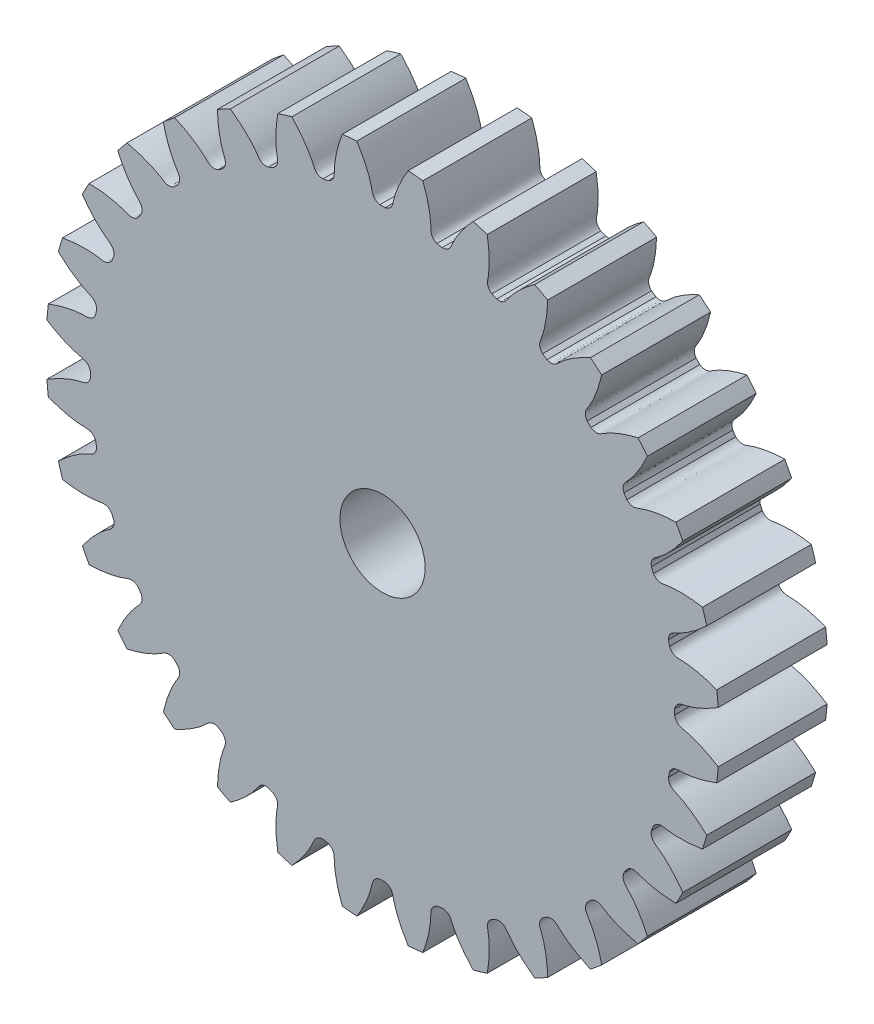
SolidWorks part; units mm, degrees
ref_plane "前视基准面" through (0, 0, 0) normal (0, 0, 1) x (1, 0, 0)
ref_plane "上视基准面" through (0, 0, 0) normal (0, 1, 0) x (1, 0, 0)
ref_plane "右视基准面" through (0, 0, 0) normal (1, 0, 0) x (0, 0, -1)
other "Configuration Table"
sketch "草图1" plane through (0, 0, 0) normal (0, 0, 1) x (1, 0, 0)
  circle A0 centre (0, 0) radius 8.5
extrude "凸台-拉伸1" add sketch "草图1" along normal blind 2.75
ref_axis "基准轴1" through (0, 0, 2.75) along (0, 0, -1)
sketch "草图2" plane through (0, 0, 0) normal (0, 0, 1) x (1, 0, 0)
  line L0 (0, 0) -> (0, 8.5) construction
  circle A0 centre (0, 0) radius 8.5 construction
  arc A1 (0.067, 7.3747) -> (-0.067, 7.3747) centre (0, 0) ccw
  arc A2 (1.6765, 9.6348) -> (-1.6765, 9.6348) centre (0, 0) ccw
  spline S0 degree 3 poles (0.067, 7.3747) (0.2444, 7.4176) (0.2542, 7.5462) (0.2867, 7.6804) (0.2952, 7.7127) (0.3051, 7.7477) (0.3166, 7.7854) (0.3299, 7.8257) (0.3449, 7.8686) (0.3618, 7.9139) (0.3807, 7.9618) (0.4017, 8.012) (0.4249, 8.0645) (0.4505, 8.1193) (0.4785, 8.1763) (0.509, 8.2353) (0.5421, 8.2964) (0.5779, 8.3594) (0.6164, 8.4243) (0.6579, 8.491) (0.7023, 8.5593) (0.7498, 8.6292) (0.8004, 8.7006) (0.8542, 8.7734) (0.9113, 8.8475) (0.9717, 8.9228) (1.0356, 8.9992) (1.1029, 9.0765) (1.1738, 9.1547) (1.2483, 9.2337) (1.3265, 9.3133) (1.4084, 9.3934) (1.5241, 9.5022) (1.6145, 9.5821) (1.6765, 9.6348) knots 0 0 0 0 0.124533 0.135329 0.147193 0.160126 0.174128 0.189198 0.205337 0.222544 0.24082 0.260164 0.280577 0.302059 0.324609 0.348227 0.372914 0.39867 0.425494 0.453386 0.482348 0.512377 0.543476 0.575642 0.608878 0.643181 0.678554 0.714995 0.752504 0.791082 0.830729 0.871444 0.913227 1 1 1 1
  spline S1 degree 3 poles (-0.067, 7.3747) (-0.2444, 7.4176) (-0.2542, 7.5462) (-0.2867, 7.6804) (-0.2952, 7.7127) (-0.3051, 7.7477) (-0.3166, 7.7854) (-0.3299, 7.8257) (-0.3449, 7.8686) (-0.3618, 7.9139) (-0.3807, 7.9618) (-0.4017, 8.012) (-0.4249, 8.0645) (-0.4505, 8.1193) (-0.4785, 8.1763) (-0.509, 8.2353) (-0.5421, 8.2964) (-0.5779, 8.3594) (-0.6164, 8.4243) (-0.6579, 8.491) (-0.7023, 8.5593) (-0.7498, 8.6292) (-0.8004, 8.7006) (-0.8542, 8.7734) (-0.9113, 8.8475) (-0.9717, 8.9228) (-1.0356, 8.9992) (-1.1029, 9.0765) (-1.1738, 9.1547) (-1.2483, 9.2337) (-1.3265, 9.3133) (-1.4084, 9.3934) (-1.5241, 9.5022) (-1.6145, 9.5821) (-1.6765, 9.6348) knots 0 0 0 0 0.124533 0.135329 0.147193 0.160126 0.174128 0.189198 0.205337 0.222544 0.24082 0.260164 0.280577 0.302059 0.324609 0.348227 0.372914 0.39867 0.425494 0.453386 0.482348 0.512377 0.543476 0.575642 0.608878 0.643181 0.678554 0.714995 0.752504 0.791082 0.830729 0.871444 0.913227 1 1 1 1
extrude "切除-拉伸1" cut sketch "草图2" along normal through all
pattern_circular "阵列(圆周)1" count 32 every 11.25 about axis through (0, 0, 2.75) along (0, 0, -1) of "切除-拉伸1"
sketch "草图3" plane through (0, 0, 0) normal (0, 0, 1) x (1, 0, 0)
  circle A0 centre (0, 0) radius 8 construction
  dimension "Dn" = 16
sketch "草图4" plane through (0, 0, 0) normal (0, 0, -1) x (-1, 0, 0)
  circle A0 centre (0, 0) radius 1.075
  dimension "D1" = 2.15
extrude "切除-拉伸2" cut sketch "草图4" against normal up to next
